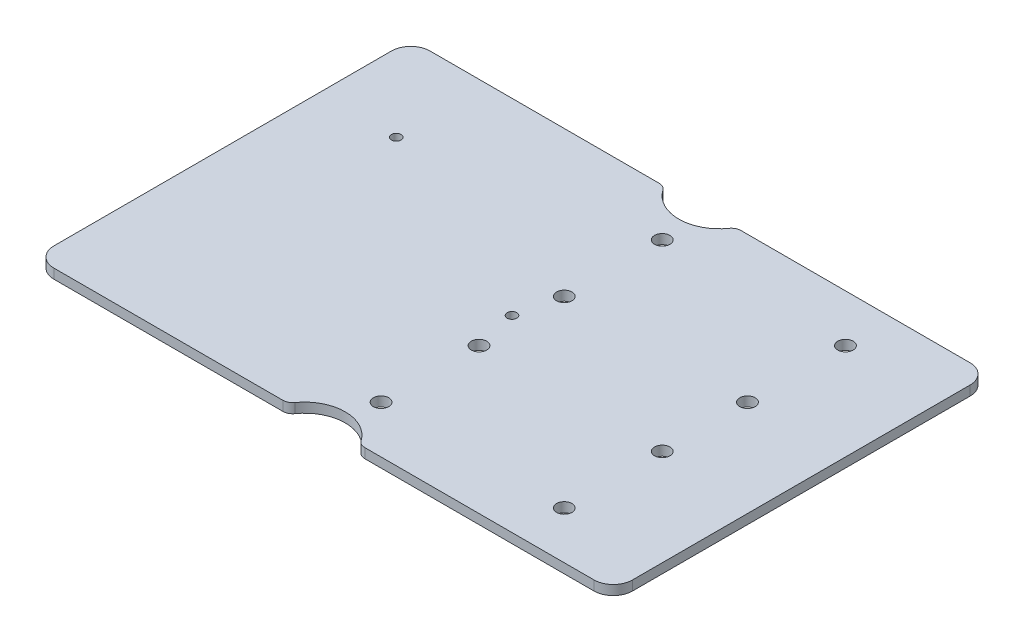
SolidWorks part; units mm, degrees
ref_plane "Front Plane" through (0, 0, 0) normal (0, 0, 1) x (1, 0, 0)
ref_plane "Top Plane" through (0, 0, 0) normal (0, 1, 0) x (1, 0, 0)
ref_plane "Right Plane" through (0, 0, 0) normal (1, 0, 0) x (0, 0, -1)
sketch "Sketch1" plane through (0, 0, 0) normal (0, 1, 0) x (1, 0, 0)
  line L1 (20, -19.5) -> (-20, -19.5)
  line L2 (20, -19.5) -> (20, 19.5)
  line L3 (20, 19.5) -> (-20, 19.5)
  line L4 (-20, -19.5) -> (-20, 19.5)
  line L5 (20, -19.5) -> (-20, 19.5) construction
  line L6 (20, 19.5) -> (-20, -19.5) construction
  point P0 (0, 0)
  dimension "D1" = 40
  dimension "D2" = 39
extrude "Boss-Extrude1" add sketch "Sketch1" along normal blind 1
sketch "Sketch2" plane through (0, 0, 0) normal (0, 1, 0) x (1, 0, 0)
  line L1 (-20, 19.5) -> (-40, 19.5)
  line L2 (-20, 19.5) -> (-20, -19.5)
  line L3 (-20, -19.5) -> (-40, -19.5)
  line L4 (-40, 19.5) -> (-40, -19.5)
  dimension "D1" = 20
extrude "Boss-Extrude2" add sketch "Sketch2" along normal up to surface (1 mm away) up to face at (0, 1, 0)
fillet "Fillet1" radius 2 4 edges at (20, 0.5, -19.5) (20, 0.5, 19.5) (-40, 0.5, -19.5) (-40, 0.5, 19.5)
sketch "Sketch3" plane through (0, 1, 0) normal (0, 1, 0) x (1, 0, 0)
  line L0 (10, -14.58) -> (10, -4.42) construction
  line L1 (-9, -14.58) -> (-9, -4.42) construction
  line L2 (17, -16.5) -> (3, -16.5) construction
  line L3 (17, -16.5) -> (17, -2.5) construction
  line L4 (17, -2.5) -> (3, -2.5) construction
  line L5 (3, -16.5) -> (3, -2.5) construction
  line L6 (17, -16.5) -> (3, -2.5) construction
  line L7 (17, -2.5) -> (3, -16.5) construction
  line L8 (-2, -16.5) -> (-16, -16.5) construction
  line L9 (-2, -16.5) -> (-2, -2.5) construction
  line L10 (-2, -2.5) -> (-16, -2.5) construction
  line L11 (-16, -16.5) -> (-16, -2.5) construction
  line L12 (-2, -16.5) -> (-16, -2.5) construction
  line L13 (-2, -2.5) -> (-16, -16.5) construction
  line L14 (-9, 4.42) -> (-9, 14.58) construction
  line L15 (-2, 2.5) -> (-16, 2.5) construction
  line L16 (-2, 2.5) -> (-2, 16.5) construction
  line L17 (-2, 16.5) -> (-16, 16.5) construction
  line L18 (-16, 2.5) -> (-16, 16.5) construction
  line L19 (-2, 2.5) -> (-16, 16.5) construction
  line L20 (-2, 16.5) -> (-16, 2.5) construction
  line L21 (10, 4.42) -> (10, 14.58) construction
  line L22 (17, 2.5) -> (3, 2.5) construction
  line L23 (17, 2.5) -> (17, 16.5) construction
  line L24 (17, 16.5) -> (3, 16.5) construction
  line L25 (3, 2.5) -> (3, 16.5) construction
  line L26 (17, 2.5) -> (3, 16.5) construction
  line L27 (17, 16.5) -> (3, 2.5) construction
  point P0 (10, -14.58)
  point P1 (10, -4.42)
  point P5 (10, -9.5)
  point P12 (-9, -14.58)
  point P13 (-9, -4.42)
  point P16 (-9, -9.5)
  point P21 (-9, 4.42)
  point P22 (-9, 14.58)
  point P25 (-9, 9.5)
  point P30 (10, 4.42)
  point P31 (10, 14.58)
  point P34 (10, 9.5)
  dimension "D1" = 10.16
  dimension "D2" = 14
  dimension "D5" = 19
  dimension "D6" = 19
  dimension "D7" = 10
  dimension "D8" = 9.5
  dimension "D3" = 2
  dimension "D4" = 2
hole_wizard "Ø1.6 (1.6) Diameter Hole1" positions "Sketch9" profile "Sketch10" hole size "Ø1.6" standard "ANSI Metric"
sketch "Sketch9" plane through (0, 1, 0) normal (0, 1, 0) x (1, 0, 0)
  point P0 (10, 14.58)
  point P3 (10, 4.42)
  point P6 (10, -4.42)
  point P9 (10, -14.58)
  point P12 (-9, -14.58)
  point P15 (-9, -4.42)
  point P18 (-9, 4.42)
  point P21 (-9, 14.58)
sketch "Sketch10" plane through (10, 1, -14.58) normal (1, 0, 0) x (0, 0, 1)
  line L0 (0, 0) -> (0, 20.2507)
  line L1 (0, 20.2507) -> (0.8, 19.77)
  line L2 (0.8, 19.77) -> (0.8, 0)
  line L5 (0.8, 0) -> (0, 0)
  line L10 (0, 20.2507) -> (-0.8, 19.77) construction
  line L11 (0, -6.35) -> (0, 107.95) construction
  dimension "Hole Dia." = 1.6
  dimension "Hole Depth" = 19.77
  dimension "Drill Angle" = 118
sketch "Sketch11" plane through (0, 0, 0) normal (0, 1, 0) x (1, 0, 0)
  line L0 (-10, -21.5) -> (-10, 21.5) construction
  line L1 (-40, 0) -> (-10, 0) construction
  line L2 (-10, 0) -> (20, 0) construction
  line L3 (-40, 17.5) -> (-40, -17.5) construction
  line L4 (20, -17.5) -> (20, 17.5) construction
  circle A0 centre (-10, -21.5) radius 4.2
  circle A1 centre (-10, 21.5) radius 4.2
  dimension "D2" = 8.4
  dimension "D1" = 43
extrude "Cut-Extrude1" cut sketch "Sketch11" along normal blind 7.4
fillet "Fillet2" radius 1 4 edges at (-13.6932, 0.5, -19.5) (-6.3068, 0.5, -19.5) (-6.3068, 0.5, 19.5) (-13.6932, 0.5, 19.5)
sketch "Sketch12" plane through (0, 0, 0) normal (0, 1, 0) x (1, 0, 0)
  circle A0 centre (-32, 10) radius 0.5
  dimension "D3" = 1
  dimension "D1" = 10
  dimension "D2" = 32
extrude "Cut-Extrude2" cut sketch "Sketch12" along normal blind 10
sketch "Sketch13" plane through (0, 0, 0) normal (0, 1, 0) x (1, 0, 0)
  line L0 (18, 19.5) -> (-5.7526, 19.5) construction
  line L1 (-40, -19.5) -> (20, -19.5)
  line L2 (-40, -19.5) -> (-40, 19.5)
  line L3 (-40, 19.5) -> (20, 19.5)
  line L4 (20, -19.5) -> (20, 19.5)
  line L5 (-40, -19.5) -> (20, 19.5) construction
  line L6 (-40, 19.5) -> (20, -19.5) construction
  line L7 (-5.7526, -19.5) -> (18, -19.5) construction
  line L8 (20, -17.5) -> (20, 17.5) construction
  line L9 (-40, 17.5) -> (-40, -17.5) construction
  point P0 (-10, 0)
ref_point "Point2"
sketch "Sketch14" plane through (0, 0, 0) normal (0, 1, 0) x (1, 0, 0)
  circle A0 centre (-10, 0) radius 0.5
  dimension "D1" = 1
extrude "Cut-Extrude3" cut sketch "Sketch14" along normal blind 10
equation "\"D8@Sketch3\"=19/2"
equation "\"D1@Cut-Extrude1\"=3.6*2+0.2"
equation "\"D2@Sketch11\"=4*2+0.4"
